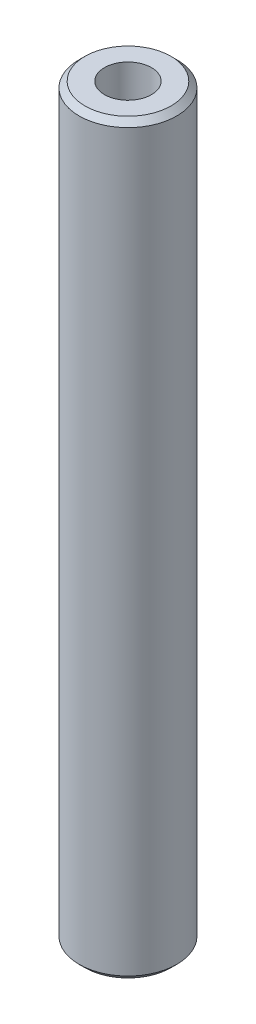
SolidWorks part; units mm, degrees
ref_plane "Front Plane" through (0, 0, 0) normal (0, 0, 1) x (1, 0, 0)
ref_plane "Top Plane" through (0, 0, 0) normal (0, 1, 0) x (1, 0, 0)
ref_plane "Right Plane" through (0, 0, 0) normal (1, 0, 0) x (0, 0, -1)
sketch "Sketch1" plane through (0, 0, 0) normal (0, 1, 0) x (1, 0, 0)
  circle A0 centre (0, 0) radius 22.5
  dimension "SHAFT_OD" = 45
extrude "Boss-Extrude1" add sketch "Sketch1" along normal blind 344.0188
sketch "Sketch2" plane through (0, 0, 0) normal (0, 1, 0) x (1, 0, 0)
  circle A0 centre (0, 0) radius 10.8215
  dimension "BORE_D" = 21.6431
extrude "Cut-Extrude1" cut sketch "Sketch2" along normal through all
chamfer "Chamfer1" distance 2.6679 angle 45 2 edges at (0, 344.0188, 22.5) (0, 0, 22.5)
